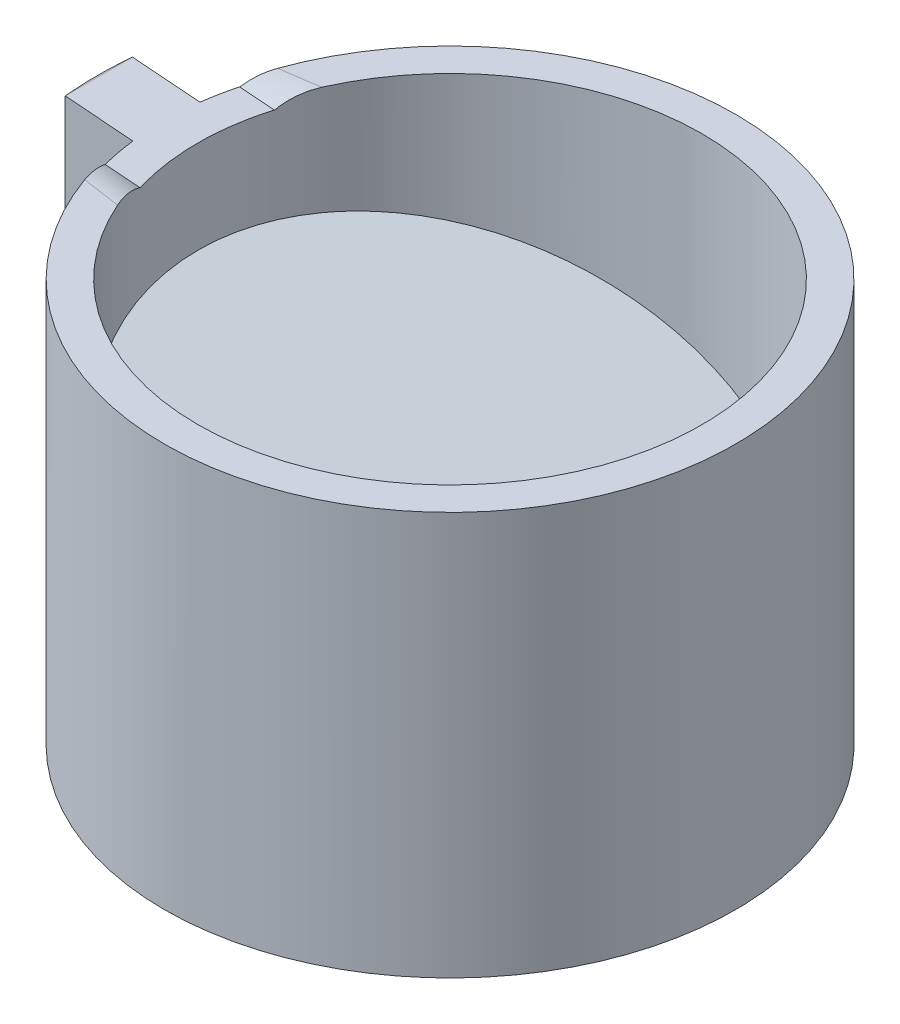
SolidWorks part; units mm, degrees
ref_plane "Front Plane" through (0, 0, 0) normal (0, 0, 1) x (1, 0, 0)
ref_plane "Top Plane" through (0, 0, 0) normal (0, 1, 0) x (1, 0, 0)
ref_plane "Right Plane" through (0, 0, 0) normal (1, 0, 0) x (0, 0, -1)
sketch "Sketch1" plane through (0, 0, 0) normal (0, 1, 0) x (1, 0, 0)
  circle A0 centre (0, 0) radius 9.525
  circle A1 centre (0, 0) radius 10.795
  dimension "D1" = 19.05
  dimension "D2" = 1.27
extrude "Boss-Extrude1" add sketch "Sketch1" along normal blind 2.54 contours A1
sketch "Sketch2" plane through (0, 2.54, 0) normal (0, 1, 0) x (1, 0, 0)
  circle A0 centre (0, 0) radius 9.525
  circle A1 centre (0, 0) radius 10.795
  circle A2 centre (0, 0) radius 10.795 construction
  dimension "D1" = 19.05
extrude "Boss-Extrude2" add sketch "Sketch2" along normal blind 12.7
ref_plane "Plane1" through (0, 12.7, 0) normal (0, 1, 0) x (1, 0, 0)
sketch "Sketch3" plane through (0, 0, 0) normal (0, 0, 1) x (1, 0, 0)
  line L1 (9.525, 2.54) -> (-9.525, 2.54) construction
  line L2 (-9.525, 11.43) -> (-9.525, 2.54)
  line L3 (-9.525, 2.54) -> (9.525, 2.54)
  line L4 (-9.525, 11.43) -> (9.525, 4.5134)
  line L5 (9.525, 4.5134) -> (9.525, 2.54)
  dimension "D1" = 8.89
  dimension "D2" = 1.9734
extrude "Boss-Extrude3" add sketch "Sketch3" along normal mid plane 19.05 contours L2 L3 L5 L4
sketch "Sketch4" plane through (0, 15.24, 0) normal (0, 1, 0) x (1, 0, 0)
  circle A0 centre (0, 0) radius 10.795
  circle A1 centre (0, 0) radius 13.4704
  circle A2 centre (0, 0) radius 10.795 construction
extrude "Cut-Extrude1" cut sketch "Sketch4" against normal up to surface (15.24 mm away) up to face at (0, 0, 10.795)
sketch "Sketch5" plane through (0, 15.24, 0) normal (0, 1, 0) x (1, 0, 0)
  line L0 (0, 0) -> (-16.3634, 0) construction
  line L2 (-9.525, 1.27) -> (-13.2744, 1.27)
  line L3 (-9.525, 1.27) -> (-9.525, -1.27)
  line L4 (-9.525, -1.27) -> (-13.2744, -1.27)
  arc A0 (-13.2744, 1.27) -> (-13.2744, -1.27) centre (0, 0) ccw
  circle A1 centre (0, 0) radius 10.795 construction
  dimension "D1" = 2.54
  dimension "D2" = 1.27
  dimension "D3" = 1.27
  dimension "D4" = 9.525
extrude "Boss-Extrude4" add sketch "Sketch5" against normal blind 5.08
sketch "Sketch7" plane through (0, 0, -1.27) normal (0, 0, -1) x (-1, 0, 0)
  line L0 (13.2744, 13.6281) -> (13.2744, 15.24)
  line L2 (13.2744, 15.24) -> (8.9498, 14.8981)
  line L6 (10.72, 15.24) -> (13.2744, 15.24) construction
  line L7 (13.2744, 10.16) -> (13.2744, 15.24) construction
  line L9 (13.2744, 15.24) -> (8.9801, 16.51)
  line L14 (8.9801, 16.51) -> (8.9498, 14.8981)
  dimension "D1" = 1.6119
  dimension "D2" = 0
  dimension "D3" = 0
  dimension "D4" = 1.6119
extrude "Cut-Extrude6" cut sketch "Sketch7" against normal blind 3.81 and the other way blind 1.27 contours L2 L14 L9
fillet "Fillet1" radius 2.54 2 edges at (-9.836, 15.24, -2.54) (-9.836, 15.24, 2.54)
